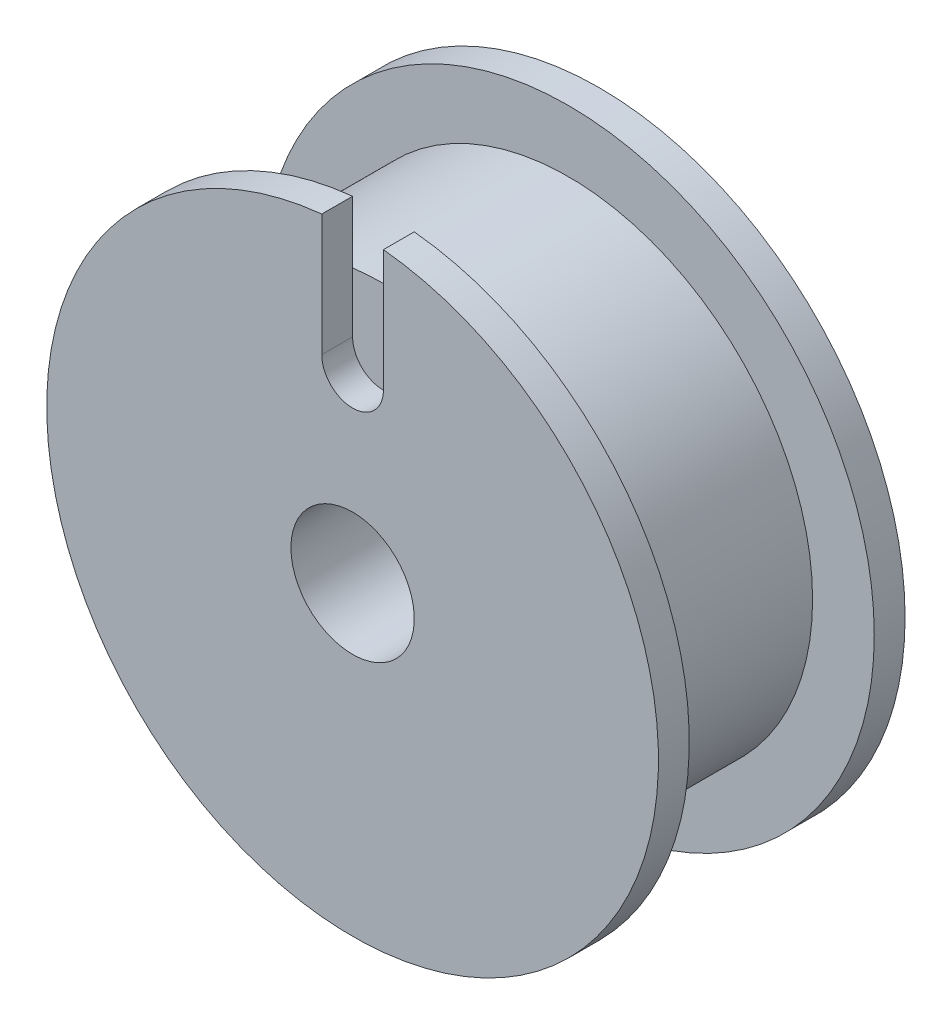
SolidWorks part; units mm, degrees
ref_plane "Front Plane" through (0, 0, 0) normal (0, 0, 1) x (1, 0, 0)
ref_plane "Top Plane" through (0, 0, 0) normal (0, 1, 0) x (1, 0, 0)
ref_plane "Right Plane" through (0, 0, 0) normal (1, 0, 0) x (0, 0, -1)
sketch "Sketch1" plane through (15.3043, 0, 0) normal (1, 0, 0) x (0, 0, -1)
  line L0 (99.7956, 24.7035) -> (-10.6045, 24.7035) construction
  line L1 (65.6556, 40.4515) -> (65.6556, 8.9555) construction
  line L2 (67.2431, 40.4515) -> (65.6556, 40.4515) construction
  line L3 (67.2431, 40.4515) -> (67.2431, 8.9555) construction
  line L4 (67.2431, 37.2765) -> (76.7681, 37.2765) construction
  line L5 (76.7681, 40.4515) -> (76.7681, 8.9555) construction
  line L6 (76.7681, 40.4515) -> (78.3556, 40.4515) construction
  line L7 (78.3556, 40.4515) -> (78.3556, 8.9555) construction
  line L8 (22.225, 24.7035) -> (9.525, 24.7035)
  line L9 (65.6556, 40.4515) -> (65.6556, 27.8785)
  line L10 (67.2431, 40.4515) -> (65.6556, 40.4515)
  line L11 (67.2431, 40.4515) -> (67.2431, 37.2765)
  line L12 (67.2431, 37.2765) -> (76.7681, 37.2765)
  line L13 (76.7681, 40.4515) -> (76.7681, 37.2765)
  line L14 (76.7681, 40.4515) -> (78.3556, 40.4515)
  line L15 (78.3556, 40.4515) -> (78.3556, 27.8785)
  line L16 (99.7956, 27.8785) -> (-1.5875, 27.8785) construction
  line L17 (99.7956, 27.8785) -> (-1.5875, 27.8785)
revolve "Revolve1" add sketch "Sketch1" angle 360 about L8 region at (15.3043, 33.0671, -72.0056)
sketch "Sketch2" plane through (0, 0, -65.6556) normal (0, 0, -1) x (-1, 0, 0)
  line L0 (-15.3043, 40.4515) -> (-15.3043, 8.9555) construction
  line L1 (-15.3043, 40.4515) -> (-15.3043, 8.9555)
  line L2 (-15.3043, 40.4515) -> (-15.3043, 34.1015) construction
  line L3 (-13.7168, 40.4515) -> (-13.7168, 34.1015)
  line L4 (-16.8918, 40.4515) -> (-16.8918, 34.1015)
  arc A0 (-13.7168, 40.4515) -> (-16.8918, 40.4515) centre (-15.3043, 40.4515) ccw
  arc A1 (-16.8918, 34.1015) -> (-13.7168, 34.1015) centre (-15.3043, 34.1015) ccw
  point P2 (-15.3043, 37.2765)
  circle M11 centre (-15.3043, 24.7035) radius 15.748
  dimension "D1" = 1.5875
  dimension "D2" = 6.35
extrude "Cut-Extrude1" cut sketch "Sketch2" along normal up to surface (1.5875 mm away) contours A1 L1 L3 M11 | A1 L4 L1 M11 region at (14.5317, 36.6314, -65.6556) region at (16.0769, 36.6314, -65.6556) up to face at (2.7313, 24.7035, -67.2431)
